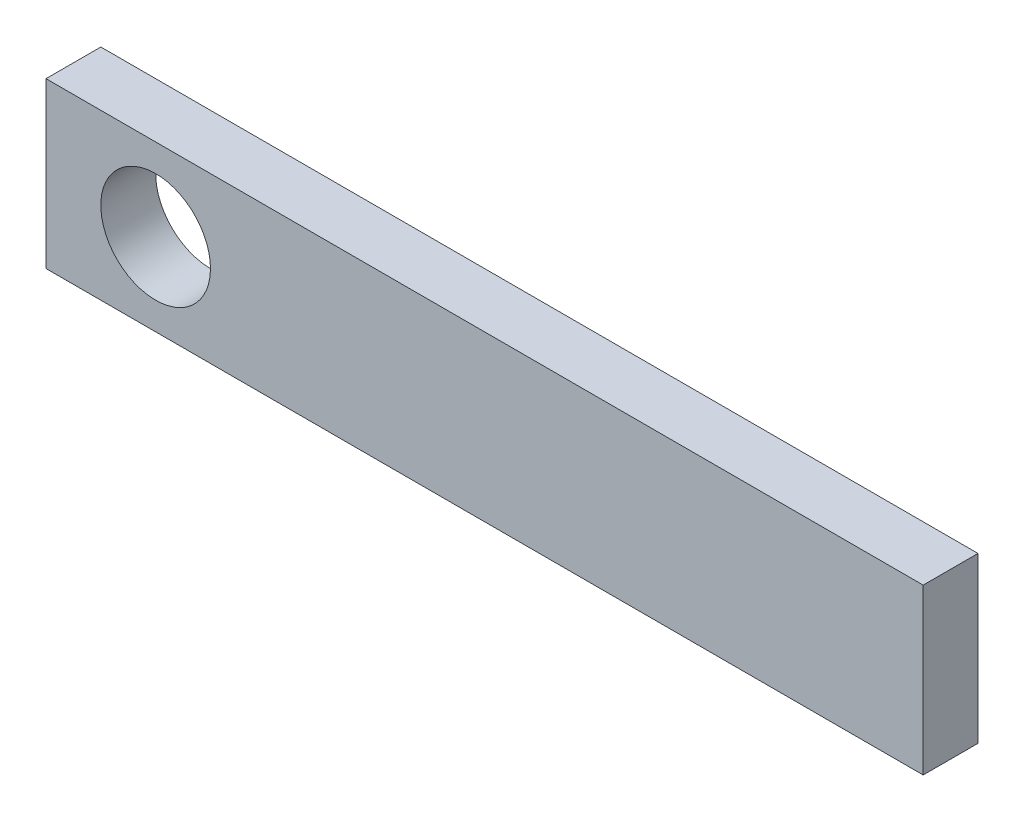
SolidWorks part; units mm, degrees
material "AISI 304"
ref_plane "Front Plane" through (0, 0, 0) normal (0, 0, 1) x (1, 0, 0)
ref_plane "Top Plane" through (0, 0, 0) normal (0, 1, 0) x (1, 0, 0)
ref_plane "Right Plane" through (0, 0, 0) normal (1, 0, 0) x (0, 0, -1)
sketch "Crank_Arm_Profile" plane through (0, 0, 0) normal (0, 0, 1) x (1, 0, 0)
  line L1 (-20, -15) -> (140, -15)
  line L2 (-20, -15) -> (-20, 15)
  line L3 (-20, 15) -> (140, 15)
  line L4 (140, -15) -> (140, 15)
  circle A0 centre (0, 0) radius 10
  dimension "Bore_Diameter" = 20
  dimension "Arm_Reach" = 140
  dimension "Bore_Diameter_2" = 20
  dimension "D4" = 15
  dimension "D5" = 15
extrude "Crank_Arm_10mm" add sketch "Crank_Arm_Profile" along normal blind 10
ref_axis "Crank_Bore_Axis" through (0, 0, -0.5) along (0, 0, 1)
ref_plane "Crank_Radius_Plane" through (120, 0, 0) normal (1, 0, 0) x (0, 0, -1)
ref_axis "Grip_Axis" through (120, 0, -0.5) along (0, 0, 1)
ref_plane "Arm_Front_Face_Plane" through (0, 0, 10) normal (0, 0, 1) x (1, 0, 0)
